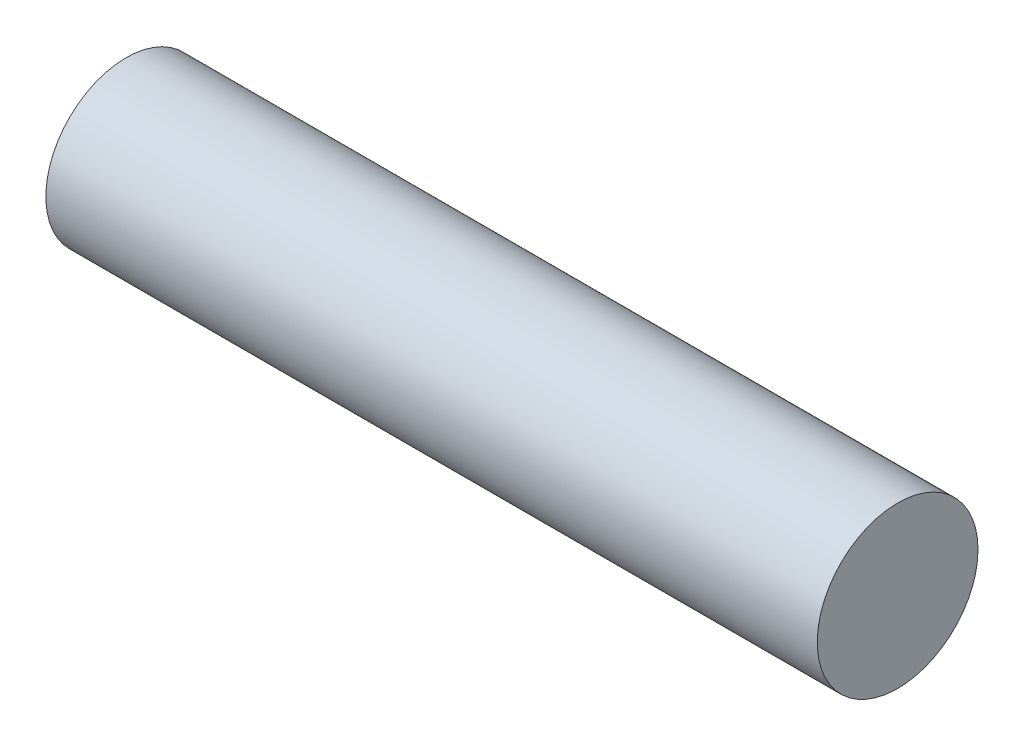
SolidWorks part; units mm, degrees
other "Title Block Table1"
other "DetailItem1"
ref_plane "Front Plane" through (0, 0, 0) normal (0, 0, 1) x (1, 0, 0)
ref_plane "Top Plane" through (0, 0, 0) normal (0, 1, 0) x (1, 0, 0)
ref_plane "Right Plane" through (0, 0, 0) normal (1, 0, 0) x (0, 0, -1)
ref_axis "X-Axis" through (-83.7009, 0, 0) along (1, 0, 0)
ref_axis "Y-Axis" through (0, 70.1691, 0) along (0, -1, 0)
ref_axis "Z-Axis" through (0, 0, -88.99) along (0, 0, 1)
sketch "Sketch1" plane through (0, 0, 0) normal (1, 0, 0) x (0, 0, -1)
  circle A0 centre (0, 0) radius 12.5
  dimension "D1" = 25
extrude "Boss-Extrude1" add sketch "Sketch1" along normal mid plane 120
